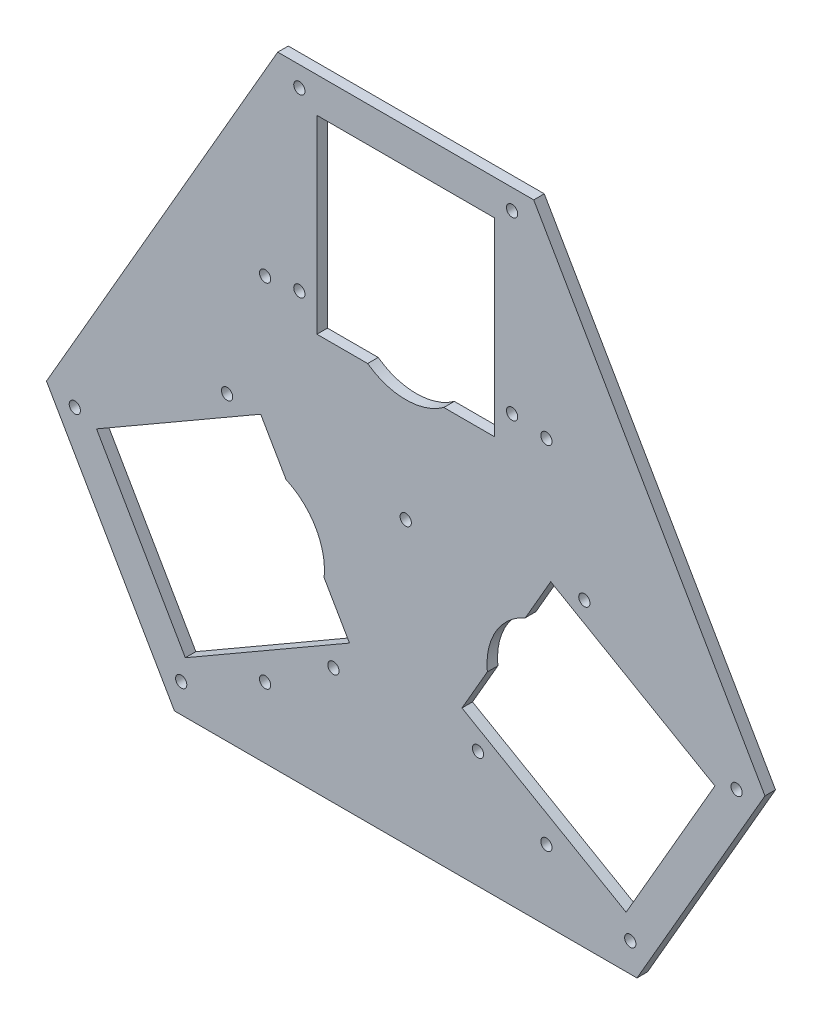
SolidWorks part; units mm, degrees
ref_plane "正面" through (0, 0, 0) normal (0, 0, 1) x (1, 0, 0)
ref_plane "平面" through (0, 0, 0) normal (0, 1, 0) x (1, 0, 0)
ref_plane "右側面" through (0, 0, 0) normal (1, 0, 0) x (0, 0, -1)
sketch "ｽｹｯﾁ1" plane through (0, 0, 0) normal (0, 0, 1) x (1, 0, 0)
  line L0 (0, -1.65) -> (0, 1.65) construction
  line L1 (-25.25, 86.9554) -> (25.25, 86.9554)
  line L2 (-25.25, 86.9554) -> (-25.25, 33.0446)
  line L3 (-25.25, 33.0446) -> (25.25, 33.0446) construction
  line L4 (25.25, 86.9554) -> (25.25, 33.0446)
  line L5 (-25.25, 86.9554) -> (25.25, 33.0446) construction
  line L6 (-25.25, 33.0446) -> (25.25, 86.9554) construction
  line L7 (0, 60) -> (0, 0) construction
  line L9 (30.25, 91.1955) -> (30.25, 41.1955) construction
  line L10 (-30.25, 91.1955) -> (-30.25, 41.1955) construction
  line L11 (87.9306, -21.6106) -> (62.6806, -65.3449)
  line L12 (87.9306, -21.6106) -> (41.2424, 5.3449)
  line L13 (62.6806, -65.3449) -> (15.9924, -38.3894)
  line L14 (41.2424, 5.3449) -> (15.9924, -38.3894) construction
  line L15 (87.9306, -21.6106) -> (15.9924, -38.3894) construction
  line L16 (41.2424, 5.3449) -> (62.6806, -65.3449) construction
  line L17 (51.9615, -30) -> (0, 0) construction
  line L18 (94.1026, -19.4005) -> (50.8013, 5.5995) construction
  line L19 (63.8526, -71.795) -> (20.5513, -46.795) construction
  line L20 (-62.6806, -65.3449) -> (-87.9306, -21.6106)
  line L21 (-62.6806, -65.3449) -> (-15.9924, -38.3894)
  line L22 (-87.9306, -21.6106) -> (-41.2424, 5.3449)
  line L23 (-15.9924, -38.3894) -> (-41.2424, 5.3449) construction
  line L24 (-62.6806, -65.3449) -> (-41.2424, 5.3449) construction
  line L25 (-15.9924, -38.3894) -> (-87.9306, -21.6106) construction
  line L26 (-51.9615, -30) -> (0, 0) construction
  line L27 (-63.8526, -71.795) -> (-20.5513, -46.795) construction
  line L28 (-94.1026, -19.4005) -> (-50.8013, 5.5995) construction
  line L29 (1.65, 0) -> (-1.65, 0) construction
  line L30 (-36.3988, 96.9554) -> (36.3988, 96.9554)
  line L31 (0, 160) -> (-138.5641, -80) construction
  line L32 (-138.5641, -80) -> (138.5641, -80) construction
  line L33 (138.5641, -80) -> (0, 160) construction
  line L34 (36.3988, 96.9554) -> (102.1653, -16.9554)
  line L35 (102.1653, -16.9554) -> (65.7665, -80)
  line L36 (65.7665, -80) -> (-65.7665, -80)
  line L37 (-65.7665, -80) -> (-102.1653, -16.9554)
  line L38 (-102.1653, -16.9554) -> (-36.3988, 96.9554)
  line L39 (-25.25, 33.0446) -> (25.25, 33.0446)
  line L40 (-40, -60) -> (40, -60) construction
  line L41 (-40, -60) -> (-40, 40) construction
  line L42 (-40, 40) -> (40, 40) construction
  line L43 (40, -60) -> (40, 40) construction
  line L44 (-40, -60) -> (40, 40) construction
  line L45 (-40, 40) -> (40, -60) construction
  line L46 (41.2424, 5.3449) -> (15.9924, -38.3894)
  line L47 (-15.9924, -38.3894) -> (-41.2424, 5.3449)
  circle A0 centre (30.25, 91.1955) radius 1.6
  circle A1 centre (30.25, 41.1955) radius 1.6
  circle A2 centre (-30.25, 41.1955) radius 1.6
  circle A3 centre (-30.25, 91.1955) radius 1.6
  circle A4 centre (63.8526, -71.795) radius 1.6
  circle A5 centre (94.1026, -19.4005) radius 1.6
  circle A6 centre (50.8013, 5.5995) radius 1.6
  circle A7 centre (20.5513, -46.795) radius 1.6
  circle A8 centre (-94.1026, -19.4005) radius 1.6
  circle A9 centre (-63.8526, -71.795) radius 1.6
  circle A10 centre (-20.5513, -46.795) radius 1.6
  circle A11 centre (-50.8013, 5.5995) radius 1.6
  circle A12 centre (0, 0) radius 80 construction
  circle A13 centre (-40, 40) radius 1.6
  circle A14 centre (40, 40) radius 1.6
  circle A15 centre (40, -60) radius 1.6
  circle A16 centre (-40, -60) radius 1.6
  circle A17 centre (0, 0) radius 1.6
  point P0 (0, 60)
  point P19 (30.25, 66.1955)
  point P46 (0, 0)
  point P48 (0, -80)
  point P59 (0, -10)
  point P71 (51.9615, -30)
  point P72 (-51.9615, -30)
  point P73 (0, 0)
  point P76 (0, 0)
  dimension "D1" = 3.2
  dimension "D12" = 3.2
  dimension "D17" = 3.2
  dimension "D2" = 50.5
  dimension "D3" = 53.9109
  dimension "D4" = 50
  dimension "D5" = 5
  dimension "D6" = 60
  dimension "D8" = 66.1955
  dimension "D9" = 80
  dimension "D10" = 10
  dimension "D11" = 10
  dimension "D13" = 100
  dimension "D14" = 80
  dimension "D15" = 0
  dimension "D7" = 3
  dimension "D16" = 3
extrude "ﾎﾞｽ - 押し出し1" add sketch "ｽｹｯﾁ1" along normal blind 3 contours L38 L37 L36 L35 L34 L30 A16 A15 A14 A13 A11 A9 A8 A7 A5 A4 A2 A1 A0 L47 L21 L20 L22 L46 L12 L11 L13 region at (0, 94.2524, 0)
sketch "ｽｹｯﾁ2" plane through (0, 0, 3) normal (0, 0, 1) x (1, 0, 0)
  line L0 (-25.25, 33.0446) -> (25.25, 33.0446) construction
  line L1 (-10.8282, 33.0446) -> (10.8282, 33.0446)
  line L4 (34.0315, -7.1448) -> (23.2033, -25.8998)
  line L5 (-23.2033, -25.8998) -> (-34.0315, -7.1448)
  arc A0 (-10.8282, 33.0446) -> (10.8282, 33.0446) centre (0, 48.0446) ccw
  arc A3 (34.0315, -7.1448) -> (23.2033, -25.8998) centre (41.6078, -24.0223) ccw
  arc A4 (-23.2033, -25.8998) -> (-34.0315, -7.1448) centre (-41.6078, -24.0223) ccw
  point P13 (-0.2887, 0.5)
  point P14 (0, 0)
  dimension "D1" = 18.5
  dimension "D2" = 15
  dimension "D3" = 3
extrude "ｶｯﾄ - 押し出し1" cut sketch "ｽｹｯﾁ2" against normal through all
equation "\"D3@ｽｹｯﾁ1\"=39/sin(50)+3"
equation "\"D8@ｽｹｯﾁ1\"=\"D6@ｽｹｯﾁ1\"+5/tan(50)+2"
